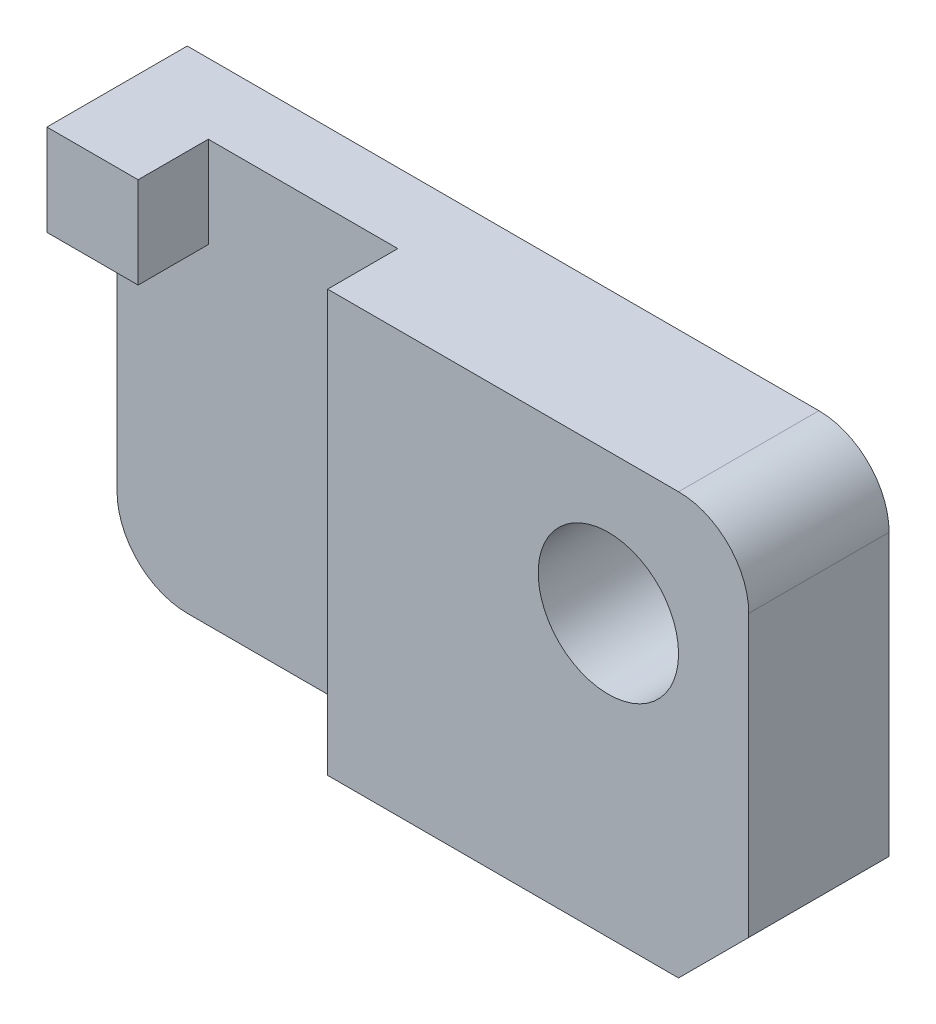
SolidWorks part; units mm, degrees
ref_plane "Front Plane" through (0, 0, 0) normal (0, 0, 1) x (1, 0, 0)
ref_plane "Top Plane" through (0, 0, 0) normal (0, 1, 0) x (1, 0, 0)
ref_plane "Right Plane" through (0, 0, 0) normal (1, 0, 0) x (0, 0, -1)
sketch "Sketch1" plane through (0, 0, 0) normal (0, 0, 1) x (1, 0, 0)
  line L0 (36.5438, 46.2033) -> (87.3438, 46.2033)
  line L1 (36.5438, 46.2033) -> (150.8438, 46.2033)
  line L2 (36.5438, 46.2033) -> (36.5438, -17.2967)
  line L3 (49.2438, -29.9967) -> (150.8438, -29.9967)
  line L4 (163.5438, 33.5033) -> (163.5438, -17.2967)
  line L5 (36.5438, 46.2033) -> (53.0538, 46.2033)
  line L6 (36.5438, 46.2033) -> (36.5438, 29.6933)
  line L7 (36.5438, 29.6933) -> (53.0538, 29.6933)
  line L8 (53.0538, 46.2033) -> (53.0538, 29.6933)
  line L9 (87.3438, 46.2033) -> (87.3438, -29.9967)
  line L16 (150.8438, -29.9967) -> (163.5438, -17.2967)
  circle A0 centre (138.1438, 20.8033) radius 12.7
  arc A1 (163.5438, 33.5033) -> (150.8438, 46.2033) centre (150.8438, 33.5033) ccw
  arc A2 (49.2438, -29.9967) -> (36.5438, -17.2967) centre (49.2438, -17.2967) cw
  point P8 (163.5438, 46.2033)
  point P18 (99.8712, 45.2313)
  point P19 (0, 0)
  dimension "D5" = 25.4
  dimension "D6" = 12.7
  dimension "D10" = 12.7
  dimension "D1" = 25.4
  dimension "D2" = 25.4
  dimension "D3" = 12.7
  dimension "D4" = 12.7
  dimension "D7" = 50.8
  dimension "D8" = 16.51
  dimension "D9" = 16.51
extrude "Boss-Extrude1" add sketch "Sketch1" along normal blind 25.4 contours L4 A1 L1 L9 L3 L16 A0 region at (123.4403, 7.1534, 0)
extrude "Boss-Extrude2" add sketch "Sketch1<4>" along normal blind 25.4 separate body contours L8 L0 L2 L7 region at (44.7988, 37.9483, 0)
sketch "Sketch1<4>" plane through (0, 0, 0) normal (0, 0, 1) x (1, 0, 0) same geometry as "Sketch1"
extrude "Boss-Extrude3" add sketch "Sketch1<5>" along normal blind 12.7 contours A2 L3 L9 L1 L8 L7 L2 region at (63.4743, 6.1631, 0)
sketch "Sketch1<5>" plane through (0, 0, 0) normal (0, 0, 1) x (1, 0, 0) same geometry as "Sketch1"
